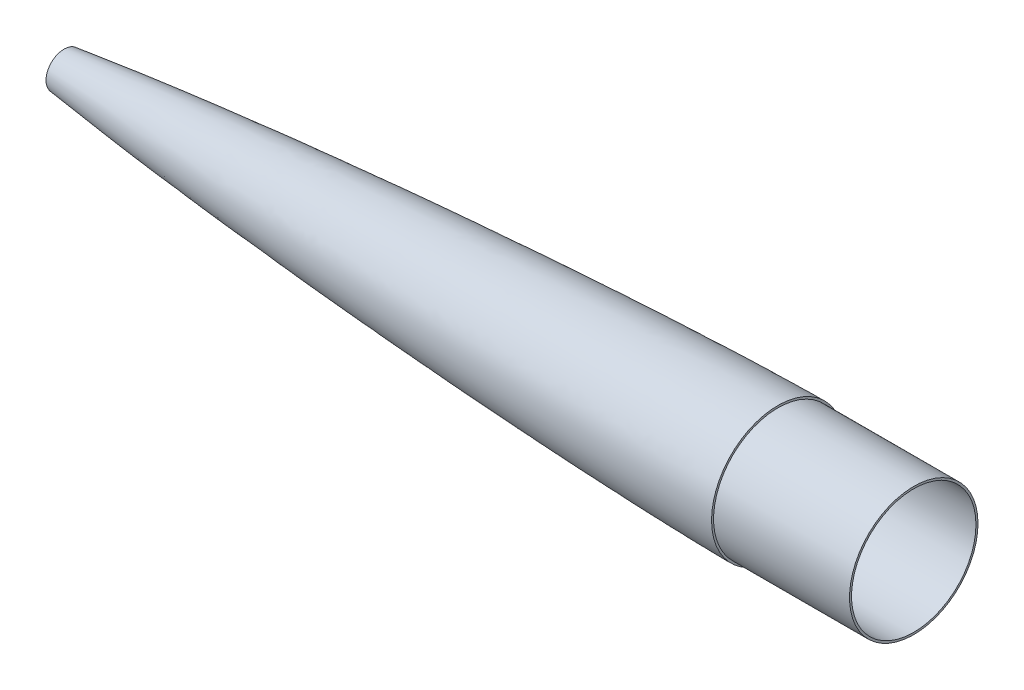
SolidWorks part; units mm, degrees
material "A-Glass Fiber"
ref_plane "Front Plane" through (0, 0, 0) normal (0, 0, 1) x (1, 0, 0)
ref_plane "Top Plane" through (0, 0, 0) normal (0, 1, 0) x (1, 0, 0)
ref_plane "Right Plane" through (0, 0, 0) normal (1, 0, 0) x (0, 0, -1)
sketch "Sketch1" plane through (0, 0, 0) normal (0, 0, 1) x (1, 0, 0)
  line L0 (609.7035, 49.5425) -> (0, 49.5425) construction
  line L1 (0, 0) -> (609.7035, 0) construction
  line L2 (609.7035, 0) -> (609.7035, 49.5425) construction
  line L4 (0, 0) -> (4.2432, 0)
  line L5 (609.7035, 49.5425) -> (609.7035, 48.0185)
  line L6 (76.2, 49.5425) -> (76.2, 0)
  line L7 (489.0535, 44.5691) -> (489.0535, 0) construction
  spline S0 degree 4 poles (0, 0) (0.0026, 0.0056) (0.0087, 0.0163) (0.0248, 0.0349) (0.0614, 0.0678) (0.1157, 0.1081) (0.188, 0.1546) (0.2908, 0.214) (0.4142, 0.2786) (0.5588, 0.3483) (0.7247, 0.4227) (0.9641, 0.524) (1.3347, 0.6697) (1.9693, 0.8979) (3.107, 1.2651) (5.1421, 1.8472) (8.9246, 2.7936) (16.0543, 4.3335) (28.7745, 6.6819) (49.7554, 9.994) (78.1202, 13.8444) (112.1347, 17.9128) (149.32, 21.9008) (186.5406, 25.5414) (223.7883, 28.8926) (261.0579, 31.9909) (298.3459, 34.8583) (335.6499, 37.5082) (372.9683, 39.947) (410.2999, 42.1753) (447.6438, 44.1872) (484.9994, 45.9696) (517.6955, 47.3072) (545.7276, 48.2682) (568.3263, 48.8964) (583.5347, 49.2341) (596.0246, 49.4397) (603.8409, 49.5199) (607.7493, 49.5425) (609.7035, 49.5425) knots 0 0 0 0 0 0.00004 0.00008 0.00016 0.000321 0.000481 0.000642 0.000936 0.00123 0.001529 0.001829 0.002633 0.003829 0.005933 0.009636 0.016455 0.029289 0.053563 0.094103 0.155164 0.216224 0.277285 0.338345 0.399406 0.460466 0.521526 0.582587 0.643647 0.704708 0.765768 0.826829 0.887889 0.918419 0.948949 0.974475 0.987237 1 1 1 1 1 construction
  spline S1 degree 4 poles (0, 0) (0.0026, 0.0056) (0.0087, 0.0163) (0.0248, 0.0349) (0.0614, 0.0678) (0.1157, 0.1081) (0.188, 0.1546) (0.2908, 0.214) (0.4142, 0.2786) (0.5588, 0.3483) (0.7247, 0.4227) (0.9641, 0.524) (1.3347, 0.6697) (1.9693, 0.8979) (3.107, 1.2651) (5.1421, 1.8472) (8.9246, 2.7936) (16.0543, 4.3335) (28.7745, 6.6819) (49.7554, 9.994) (78.1202, 13.8444) (112.1347, 17.9128) (149.32, 21.9008) (186.5406, 25.5414) (223.7883, 28.8926) (261.0579, 31.9909) (298.3459, 34.8583) (335.6499, 37.5082) (372.9683, 39.947) (410.2999, 42.1753) (447.6438, 44.1872) (484.9994, 45.9696) (517.6955, 47.3072) (545.7276, 48.2682) (568.3263, 48.8964) (583.5347, 49.2341) (596.0246, 49.4397) (603.8409, 49.5199) (607.7493, 49.5425) (609.7035, 49.5425) knots 0 0 0 0 0 0.00004 0.00008 0.00016 0.000321 0.000481 0.000642 0.000936 0.00123 0.001529 0.001829 0.002633 0.003829 0.005933 0.009636 0.016455 0.029289 0.053563 0.094103 0.155164 0.216224 0.277285 0.338345 0.399406 0.460466 0.521526 0.582587 0.643647 0.704708 0.765768 0.826829 0.887889 0.918419 0.948949 0.974475 0.987237 1 1 1 1 1
  spline S2 degree 1 poles (1.0385, -1.1154) (609.7035, 48.0185) knots 0 0 1 1 construction
  spline S3 degree 3 poles (1.0385, -1.1154) (1.0989, -1.083) (1.2128, -1.0279) (1.5232, -0.8922) (2.1055, -0.6677) (2.9562, -0.3824) (3.8274, -0.1188) (4.5739, 0.0949) (5.7537, 0.4193) (7.5186, 0.8678) (10.5921, 1.5877) (14.4643, 2.4134) (19.1367, 3.3301) (23.8239, 4.1916) (30.089, 5.283) (37.9399, 6.5629) (47.381, 7.9992) (59.9884, 9.8123) (75.7734, 11.9237) (94.7431, 14.2755) (113.7321, 16.4844) (132.7363, 18.5735) (158.0914, 21.2218) (189.8103, 24.3062) (227.9026, 27.7085) (266.0186, 30.8488) (304.1542, 33.7496) (342.3067, 36.4242) (393.1966, 39.6957) (438.932, 42.2396) (478.3176, 44.1042) (503.7895, 45.214) (534.4517, 46.3896) (565.1178, 47.3188) (590.6059, 47.8413) (603.3361, 48.0185) (609.7035, 48.0185) knots 0.000645 0.000645 0.000645 0.000645 0.001133 0.001621 0.002597 0.004549 0.006234 0.00721 0.008452 0.012356 0.01626 0.024067 0.031875 0.039682 0.04749 0.063105 0.078719 0.094334 0.125564 0.156794 0.188024 0.219254 0.250484 0.312943 0.375403 0.437863 0.500322 0.562782 0.625242 0.750161 0.787197 0.818427 0.875081 0.93754 0.96877 1 1 1 1
  dimension "D1" = 1.524
  dimension "D2" = 76.2
  dimension "D3" = 120.65
revolve "Revolve1" add sketch "Sketch1" angle 360 about L1 region at (342.553, 37.3951, 0)
sketch "Sketch2" plane through (609.7035, 0, 0) normal (1, 0, 0) x (0, 0, -1)
  circle A0 centre (0, 0) radius 48.0185
  circle A2 centre (0, 0) radius 48.0185 construction
  circle A4 centre (0, 0) radius 46.4945
  dimension "D1" = 1.524
extrude "Boss-Extrude1" add sketch "Sketch2" along normal blind 101.6 and the other way blind 25.4
sketch "Sketch3" [suppressed] plane through (0, 0, 0) normal (0, 0, 1) x (1, 0, 0)
  line L1 (609.7035, -6.35) -> (704.9535, -6.35)
  line L2 (609.7035, -6.35) -> (609.7035, 6.35)
  line L3 (609.7035, 6.35) -> (704.9535, 6.35)
  line L4 (704.9535, -6.35) -> (704.9535, 6.35)
  line L5 (609.7035, -6.35) -> (704.9535, 6.35) construction
  line L6 (609.7035, 6.35) -> (704.9535, -6.35) construction
  line L7 (711.3035, -48.0185) -> (711.3035, 48.0185) construction
  line L8 (54.4968, 0) -> (-54.4968, 0) construction
  line L9 (609.7035, -48.0185) -> (609.7035, 48.0185) construction
  point P0 (657.3285, 0)
  dimension "D2" = 12.7
  dimension "D3" = 6.35
extrude "Cut-Extrude1" [suppressed] cut sketch "Sketch3" along normal through all
pattern_circular "CirPattern1" [suppressed] count 3 every 120 of bodies 103
